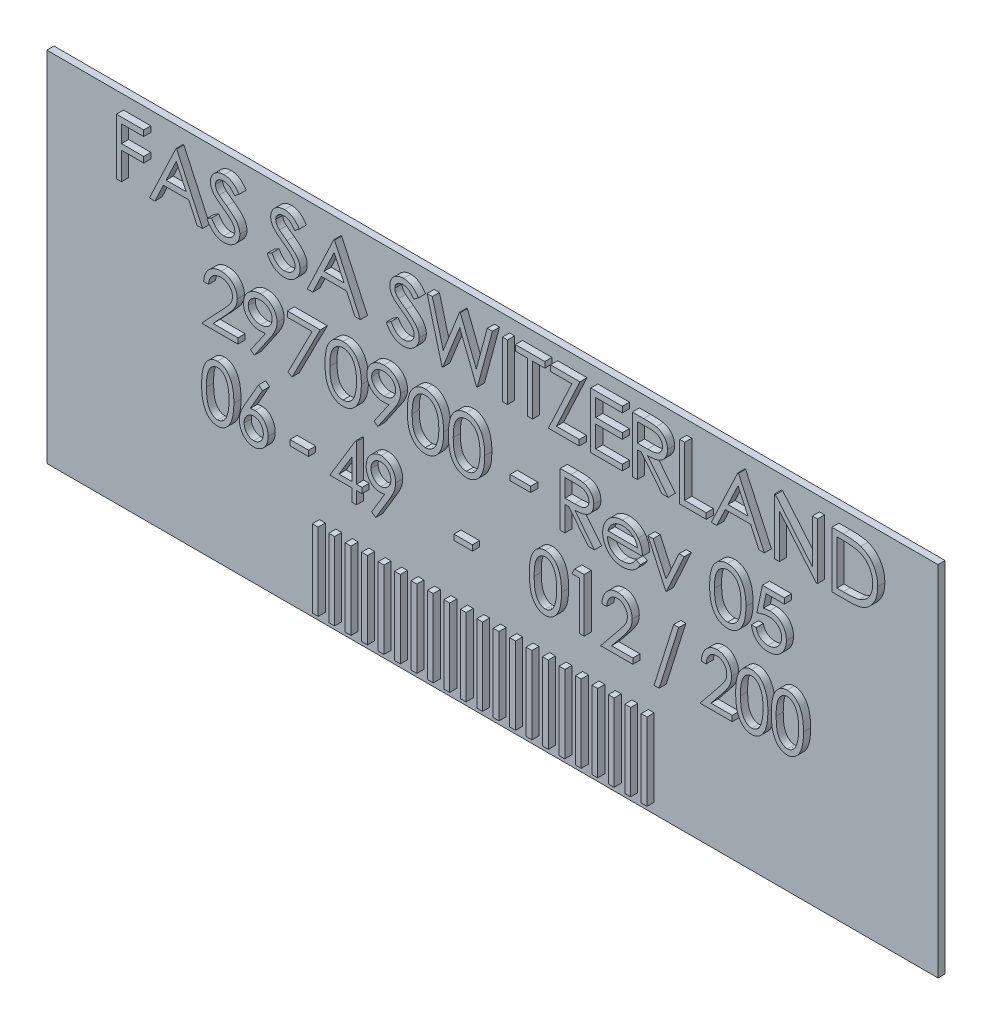
SolidWorks part; units mm, degrees
material "ABS"
ref_plane "Plan de face" through (0, 0, 0) normal (0, 0, 1) x (1, 0, 0)
ref_plane "Plan de dessus" through (0, 0, 0) normal (0, 1, 0) x (1, 0, 0)
ref_plane "Plan de droite" through (0, 0, 0) normal (1, 0, 0) x (0, 0, -1)
sketch "Esquisse1" plane through (0, 0, 0) normal (0, 0, 1) x (1, 0, 0)
  line L1 (-22.4844, -2.8351) -> (2.5156, -2.8351)
  line L2 (-22.4844, -2.8351) -> (-22.4844, -12.8776)
  line L3 (-22.4844, -12.8776) -> (2.5156, -12.8776)
  line L4 (2.5156, -2.8351) -> (2.5156, -12.8776)
  dimension "D1" = 10.0425
  dimension "D2" = 25
extrude "Extrusion1" add sketch "Esquisse1" along normal blind 0.2
sketch "Esquisse2" plane through (0, 0, 0.2) normal (0, 0, 1) x (1, 0, 0)
  text T0 "FAS SA SWITZERLAND\r\n" font "Century Gothic" height 1.57
extrude "Extrusion2" add sketch "Esquisse2" along normal blind 0.2
sketch "Esquisse3" plane through (0, 0, 0.2) normal (0, 0, 1) x (1, 0, 0)
  text T0 "2970900 - Rev 05" font "Century Gothic" height 1.5
extrude "Extrusion3" add sketch "Esquisse3" along normal blind 0.2
sketch "Esquisse4" plane through (0, 0, 0.2) normal (0, 0, 1) x (1, 0, 0)
  text T0 "06 - 49   -   012 / 200" font "Century Gothic" height 1.5
extrude "Extrusion4" add sketch "Esquisse4" along normal blind 0.2
sketch "Esquisse6" plane through (0, 0, 0.2) normal (0, 0, 1) x (1, 0, 0)
  text T0 "lllllllllllllllllllll" font "Century Gothic" height in points 8
extrude "Extrusion6" add sketch "Esquisse6" along normal blind 0.2
